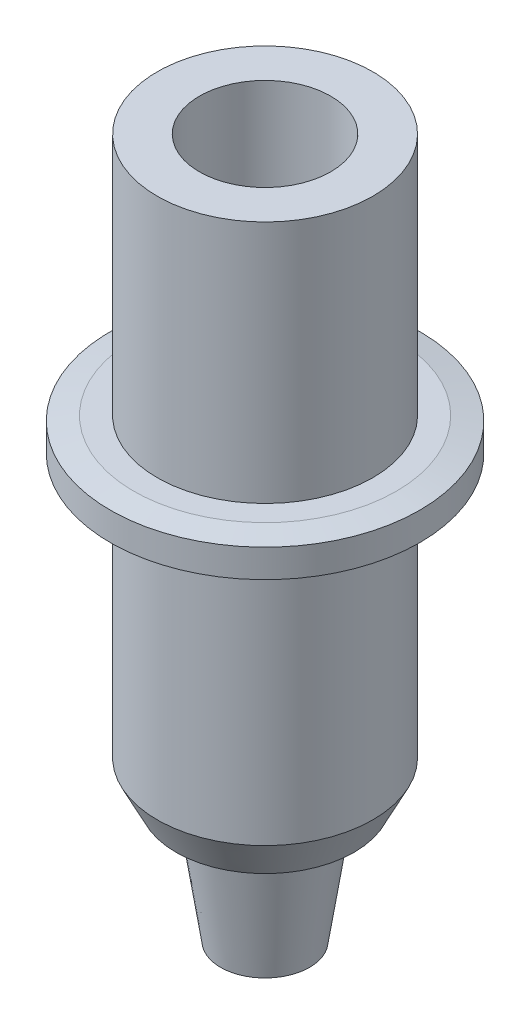
SolidWorks part; units mm, degrees
ref_plane "Front Plane" through (0, 0, 0) normal (0, 0, 1) x (1, 0, 0)
ref_plane "Top Plane" through (0, 0, 0) normal (0, 1, 0) x (1, 0, 0)
ref_plane "Right Plane" through (0, 0, 0) normal (1, 0, 0) x (0, 0, -1)
sketch "Sketch1" plane through (0, 0, 0) normal (0, 0, 1) x (1, 0, 0)
  line L0 (0, -143.9505) -> (0, 7053.5726) construction
  line L1 (0, 0) -> (2.375, 0)
  line L2 (2.375, 0) -> (3.2, 5.5)
  line L3 (3.2, 5.5) -> (3.2, 6.5)
  line L4 (3.2, 6.5) -> (4.75, 6.5)
  line L5 (4.75, 6.5) -> (5.75, 8.5)
  line L6 (5.75, 8.5) -> (5.75, 22.3)
  line L7 (5.75, 22.3) -> (7, 22.3)
  line L8 (7, 22.3) -> (8.25, 22.55)
  line L9 (8.25, 22.55) -> (8.25, 24.05)
  line L10 (8.25, 24.05) -> (7, 24.3)
  line L11 (7, 24.3) -> (5.75, 24.3)
  line L12 (5.75, 24.3) -> (5.75, 37.3)
  line L13 (5.75, 37.3) -> (0, 37.3)
  line L14 (0, 37.3) -> (0, 0)
  point P18 (0, 37.3)
  point P29 (0, 0)
  dimension "D2" = 15.8
  dimension "D3" = 11.5
  dimension "D4" = 2
  dimension "D5" = 1.5
  dimension "D6" = 16.5
  dimension "D7" = 6.5
  dimension "D8" = 1
  dimension "D9" = 6.4
  dimension "D10" = 4.75
  dimension "D11" = 2
  dimension "D12" = 1.25
  dimension "D13" = 13
  dimension "D14" = 9.5
revolve "Revolve1" add sketch "Sketch1" angle 360 about L0
sketch "Sketch2" plane through (0, 0, 0) normal (0, 0, 1) x (1, 0, 0)
  line L0 (1.2, 0) -> (1.2, 2)
  line L1 (1.2, 2) -> (2.25, 2)
  line L2 (2.25, 2) -> (2.25, 14.18)
  line L3 (2.25, 14.18) -> (3.5, 14.18)
  line L4 (3.5, 14.18) -> (3.5, 37.3)
  line L5 (3.5, 37.3) -> (0, 37.3)
  line L6 (0, -1000) -> (0, 49000) construction
  line L7 (1.2, 0) -> (0, 0)
  line L8 (5.75, 37.3) -> (-5.75, 37.3) construction
  line L9 (-2.375, 0) -> (2.375, 0) construction
  line L10 (0, 37.3) -> (0, 0)
  dimension "D1" = 7
  dimension "D2" = 14.18
  dimension "D3" = 4.5
  dimension "D4" = 2.4
  dimension "D5" = 2
revolve "Cut-Revolve1" cut sketch "Sketch2" angle 360 about L6
